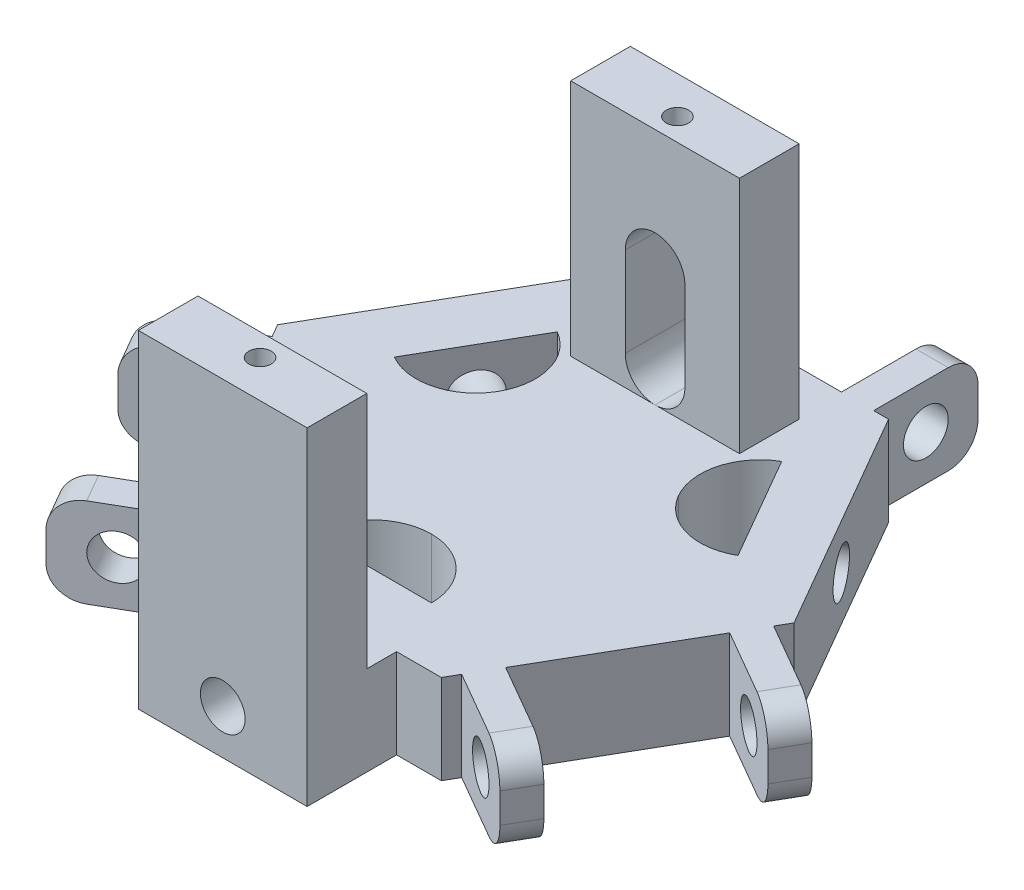
SolidWorks part; units mm, degrees
ref_plane "Front Plane" through (0, 0, 0) normal (0, 0, 1) x (1, 0, 0)
ref_plane "Top Plane" through (0, 0, 0) normal (0, 1, 0) x (1, 0, 0)
ref_plane "Right Plane" through (0, 0, 0) normal (1, 0, 0) x (0, 0, -1)
sketch "Sketch1" plane through (0, 0, 0) normal (0, 1, 0) x (1, 0, 0)
  line L1 (17.3205, 0) -> (8.6603, 15)
  line L2 (8.6603, 15) -> (-8.6603, 15)
  line L3 (-8.6603, 15) -> (-17.3205, 0)
  line L4 (-17.3205, 0) -> (-8.6603, -15)
  line L5 (-8.6603, -15) -> (8.6603, -15)
  line L6 (8.6603, -15) -> (17.3205, 0)
  circle A0 centre (0, 0) radius 15 construction
  dimension "D1" = 30
extrude "Boss-Extrude1" add sketch "Sketch1" along normal blind 6
sketch "Sketch2" plane through (12.9904, 0, 7.5) normal (0.866, 0, 0.5) x (0.5, 0, -0.866)
  line L0 (-8.6603, 6) -> (8.6603, 6) construction
  line L1 (-5.5003, 6) -> (-7.6603, 6)
  line L2 (-5.5003, 6) -> (-5.5003, 0)
  line L3 (-5.5003, 0) -> (-7.6603, 0)
  line L4 (-7.6603, 6) -> (-7.6603, 0)
  line L5 (-8.6603, 0) -> (8.6603, 0) construction
  line L6 (-8.6603, 6) -> (-8.6603, 0) construction
  dimension "D1" = 2.16
  dimension "D2" = 1
extrude "Boss-Extrude2" add sketch "Sketch2" along normal blind 7
sketch "Sketch4" plane through (12.9904, 0, 7.5) normal (0.866, 0, 0.5) x (0.5, 0, -0.866)
  line L0 (-5.5003, 6) -> (8.6603, 6) construction
  line L1 (5.5003, 6) -> (7.6603, 6)
  line L2 (5.5003, 6) -> (5.5003, 0)
  line L3 (5.5003, 0) -> (7.6603, 0)
  line L4 (7.6603, 6) -> (7.6603, 0)
  line L5 (-5.5003, 0) -> (8.6603, 0) construction
  line L6 (8.6603, 6) -> (8.6603, 0) construction
  dimension "D1" = 1
  dimension "D2" = 2.16
extrude "Boss-Extrude3" add sketch "Sketch4" along normal blind 7
sketch "Sketch5" plane through (-12.9904, 0, 7.5) normal (-0.866, 0, 0.5) x (0.5, 0, 0.866)
  line L0 (-8.6603, 6) -> (8.6603, 6) construction
  line L1 (-7.6603, 6) -> (-5.5003, 6)
  line L2 (-7.6603, 6) -> (-7.6603, 0)
  line L3 (-7.6603, 0) -> (-5.5003, 0)
  line L4 (-5.5003, 6) -> (-5.5003, 0)
  line L5 (-8.6603, 0) -> (8.6603, 0) construction
  line L6 (-8.6603, 6) -> (-8.6603, 0) construction
  dimension "D1" = 1
  dimension "D2" = 2.16
extrude "Boss-Extrude4" add sketch "Sketch5" along normal blind 7
sketch "Sketch6" plane through (-12.9904, 0, 7.5) normal (-0.866, 0, 0.5) x (0.5, 0, 0.866)
  line L0 (-5.5003, 6) -> (8.6603, 6) construction
  line L1 (5.5003, 6) -> (7.6603, 6)
  line L2 (5.5003, 6) -> (5.5003, 0)
  line L3 (5.5003, 0) -> (7.6603, 0)
  line L4 (7.6603, 6) -> (7.6603, 0)
  line L5 (-5.5003, 0) -> (8.6603, 0) construction
  line L6 (8.6603, 6) -> (8.6603, 0) construction
  dimension "D1" = 1
  dimension "D2" = 2.16
extrude "Boss-Extrude5" add sketch "Sketch6" along normal blind 7
sketch "Sketch7" plane through (0, 0, -15) normal (0, 0, -1) x (-1, 0, 0)
  line L0 (-8.6603, 6) -> (8.6603, 6) construction
  line L1 (-5.5003, 6) -> (-7.6603, 6)
  line L2 (-5.5003, 6) -> (-5.5003, 0)
  line L3 (-5.5003, 0) -> (-7.6603, 0)
  line L4 (-7.6603, 6) -> (-7.6603, 0)
  line L5 (-8.6603, 0) -> (8.6603, 0) construction
  line L6 (-8.6603, 6) -> (-8.6603, 0) construction
  dimension "D1" = 1
  dimension "D2" = 2.16
extrude "Boss-Extrude6" add sketch "Sketch7" along normal blind 7
sketch "Sketch9" plane through (0, 0, -15) normal (0, 0, -1) x (-1, 0, 0)
  line L0 (-5.5003, 6) -> (8.6603, 6) construction
  line L1 (5.5003, 6) -> (7.6603, 6)
  line L2 (5.5003, 6) -> (5.5003, 0)
  line L3 (5.5003, 0) -> (7.6603, 0)
  line L4 (7.6603, 6) -> (7.6603, 0)
  line L5 (-5.5003, 0) -> (8.6603, 0) construction
  line L6 (8.6603, 6) -> (8.6603, 0) construction
  dimension "D1" = 1
  dimension "D2" = 2.16
extrude "Boss-Extrude7" add sketch "Sketch9" along normal blind 7
sketch "Sketch11" plane through (0, 0, 15) normal (0, 0, 1) x (1, 0, 0)
  line L0 (-8.6603, 0) -> (8.6603, 0) construction
  line L1 (-5.6603, 0) -> (5.6603, 0)
  line L2 (-5.6603, 0) -> (-5.6603, 22)
  line L3 (-5.6603, 22) -> (5.6603, 22)
  line L4 (5.6603, 0) -> (5.6603, 22)
  line L5 (-8.6603, 6) -> (-8.6603, 0) construction
  line L6 (8.6603, 6) -> (8.6603, 0) construction
  point P10 (8.6603, 3)
  dimension "D1" = 22
  dimension "D2" = 3
  dimension "D3" = 3
extrude "Boss-Extrude8" add sketch "Sketch11" along normal blind 6
sketch "Sketch13" plane through (0, 22, 0) normal (0, 1, 0) x (1, 0, 0)
  line L0 (5.6603, -21) -> (5.6603, -15) construction
  line L1 (-5.6603, -15) -> (5.6603, -15)
  line L2 (-5.6603, -15) -> (-5.6603, -17)
  line L3 (-5.6603, -17) -> (5.6603, -17)
  line L4 (5.6603, -15) -> (5.6603, -17)
  dimension "D1" = 2
extrude "Cut-Extrude1" cut sketch "Sketch13" against normal blind 16
sketch "Sketch14" plane through (0, 6, 0) normal (0, 1, 0) x (1, 0, 0)
  line L0 (5.5003, 15) -> (-5.5003, 15) construction
  line L1 (-5.6603, 12) -> (5.6603, 12)
  line L2 (-5.6603, 12) -> (-5.6603, 8)
  line L3 (-5.6603, 8) -> (5.6603, 8)
  line L4 (5.6603, 12) -> (5.6603, 8)
  line L5 (5.6603, -17) -> (5.6603, -15) construction
  line L6 (-5.6603, -15) -> (-5.6603, -17) construction
  dimension "D1" = 4
  dimension "D2" = 3
  dimension "D3" = 0
  dimension "D4" = 0
extrude "Boss-Extrude9" add sketch "Sketch14" along normal blind 16
sketch "Sketch22" plane through (0, 0, -12) normal (0, 0, -1) x (-1, 0, 0)
  line L0 (-5.6603, 6) -> (5.6603, 6) construction
  line L1 (-1.9997, 16) -> (2.0003, 16)
  line L2 (-1.9997, 16) -> (-1.9997, 6)
  line L3 (-1.9997, 6) -> (2.0003, 6)
  line L4 (2.0003, 16) -> (2.0003, 6)
  line L5 (5.6603, 22) -> (5.6603, 6) construction
  dimension "D1" = 10
  dimension "D2" = 4
  dimension "D3" = 3.66
extrude "Cut-Extrude8" cut sketch "Sketch22" against normal blind 4
sketch "Sketch23" plane through (7.6603, 0, 0) normal (1, 0, 0) x (0, 0, -1)
  line L0 (22, 0) -> (15, 6) construction
  line L1 (15, 0) -> (22, 6) construction
  circle A0 centre (18.5, 3) radius 1.5
  dimension "D1" = 3
extrude "Cut-Extrude9" cut sketch "Sketch23" against normal through all
sketch "Sketch24" plane through (-3.8301, 0, 6.634) normal (-0.5, 0, 0.866) x (0.866, 0, 0.5)
  line L0 (22, 0) -> (15, 6) construction
  line L1 (15, 0) -> (22, 6) construction
  circle A0 centre (18.5, 3) radius 1.5
  dimension "D1" = 3
extrude "Cut-Extrude10" cut sketch "Sketch24" against normal through all
sketch "Sketch25" plane through (-3.8301, 0, -6.634) normal (-0.5, 0, -0.866) x (-0.866, 0, 0.5)
  line L0 (22, 0) -> (15, 6) construction
  line L1 (15, 0) -> (22, 6) construction
  circle A0 centre (18.5, 3) radius 1.5
  dimension "D1" = 3
extrude "Cut-Extrude11" cut sketch "Sketch25" against normal through all
sketch "Sketch26" plane through (0, 6, 0) normal (0, 1, 0) x (1, 0, 0)
  line L0 (-5.6603, -15) -> (-5.6603, -17) construction
  line L1 (-4.0003, -7) -> (3.9997, -7)
  line L2 (-4.0003, -7) -> (-4.0003, -11)
  line L3 (-4.0003, -11) -> (3.9997, -11)
  line L4 (3.9997, -7) -> (3.9997, -11)
  line L5 (-8.6603, -15) -> (-5.6603, -15) construction
  dimension "D1" = 8
  dimension "D2" = 1.66
  dimension "D3" = 4
  dimension "D4" = 4
extrude "Cut-Extrude12" cut sketch "Sketch26" against normal blind 6 contours L2 L1 L4 L3
fillet "Fillet1" radius 4 2 edges at (-4.0003, 3, 7) (3.9997, 3, 7)
sketch "Sketch32" plane through (0, 6, 0) normal (0, 1, 0) x (1, 0, 0)
  line L0 (10.9903, 10.9643) -> (14.9905, 4.0357)
  line L1 (10.9903, 10.9643) -> (7.5262, 8.9643)
  line L2 (14.9905, 4.0357) -> (11.5264, 2.0357)
  line L3 (7.5262, 8.9643) -> (11.5264, 2.0357)
  line L4 (17.3205, 0) -> (8.6603, 15) construction
  line L5 (7.5262, 8.9643) -> (11.5264, 2.0357)
  line L6 (7.5262, 8.9643) -> (4.0621, 6.9643)
  line L7 (11.5264, 2.0357) -> (8.0623, 0.0357)
  line L8 (4.0621, 6.9643) -> (8.0623, 0.0357)
  dimension "D1" = 4
  dimension "D2" = 4.66
  dimension "D3" = 4.66
  dimension "D4" = 4
extrude "Cut-Extrude13" cut sketch "Sketch32" against normal blind 6 contours L6 L8 L7 L3 region at (7.7942, 6, -4.5)
fillet "Fillet2" radius 4 2 edges at (8.0623, 3, -0.0357) (4.0621, 3, -6.9643)
sketch "Sketch33" plane through (0, 6, 0) normal (0, 1, 0) x (1, 0, 0)
  line L0 (-14.9905, 4.0357) -> (-10.9905, 10.9639)
  line L1 (-14.9905, 4.0357) -> (-11.5264, 2.0357)
  line L2 (-10.9905, 10.9639) -> (-7.5264, 8.9639)
  line L3 (-11.5264, 2.0357) -> (-7.5264, 8.9639)
  line L4 (-8.6603, 15) -> (-17.3205, 0) construction
  line L5 (-7.5264, 8.9639) -> (-11.5264, 2.0357)
  line L6 (-7.5264, 8.9639) -> (-4.0623, 6.9639)
  line L7 (-11.5264, 2.0357) -> (-8.0623, 0.0357)
  line L8 (-4.0623, 6.9639) -> (-8.0623, 0.0357)
  dimension "D1" = 8
  dimension "D2" = 4
  dimension "D3" = 4.66
  dimension "D4" = 4
extrude "Cut-Extrude14" cut sketch "Sketch33" against normal blind 6 contours L5 L6 L8 L7
fillet "Fillet3" radius 4 2 edges at (-8.0623, 3, -0.0357) (-4.0623, 3, -6.9639)
sketch "Sketch34" plane through (-12.9904, 0, -7.5) normal (-0.866, 0, -0.5) x (-0.5, 0, 0.866)
  line L0 (8.6603, 6) -> (-8.6603, 0) construction
  line L1 (-8.4772, 6) -> (8.6603, 0) construction
  line L2 (-9.3922, 6) -> (-7.5622, 6) construction
  circle A0 centre (0, 3) radius 1.5
  dimension "D1" = 3
extrude "Cut-Extrude15" cut sketch "Sketch34" against normal blind 4
sketch "Sketch35" plane through (12.9904, 0, -7.5) normal (0.866, 0, -0.5) x (-0.5, 0, -0.866)
  line L0 (8.6603, 6) -> (-8.6603, 0) construction
  line L1 (-8.6603, 6) -> (8.6603, 0) construction
  circle A0 centre (0, 3) radius 1.5
  dimension "D1" = 3
extrude "Cut-Extrude16" cut sketch "Sketch35" against normal blind 4
sketch "Sketch36" plane through (0, 0, 21) normal (0, 0, 1) x (1, 0, 0)
  line L0 (-5.6603, 6) -> (5.6603, 0) construction
  line L1 (-5.6603, 0) -> (5.6603, 6) construction
  circle A0 centre (0, 3) radius 1.5
  dimension "D1" = 3
extrude "Cut-Extrude17" cut sketch "Sketch36" against normal blind 10
fillet "Fillet4" radius 2 2 edges at (1.9997, 16, -10) (-2.0003, 16, -10)
fillet "Fillet5" radius 2 2 edges at (-2.0003, 6, -10) (1.9997, 6, -10)
sketch "Sketch37" plane through (0, 22, 0) normal (0, 1, 0) x (1, 0, 0)
  line L0 (-5.6603, 8) -> (5.6603, 8) construction
  circle A0 centre (0, 9.5) radius 0.75
  dimension "D1" = 1.5
  dimension "D2" = 1.5
extrude "Cut-Extrude19" cut sketch "Sketch37" against normal blind 5
sketch "Sketch39" plane through (0, 22, 0) normal (0, 1, 0) x (1, 0, 0)
  line L0 (-5.6603, -17) -> (5.6603, -17) construction
  circle A0 centre (0, -18.5) radius 0.75
  dimension "D1" = 1.5
  dimension "D2" = 1.5
extrude "Cut-Extrude20" cut sketch "Sketch39" against normal blind 5
fillet "Fillet6" radius 2 12 edges at (-22.3427, 0, 5.3013) (-22.3427, 6, 5.3013) (-15.7624, 0, 16.6987) (-15.7624, 6, 16.6987) (15.7624, 6, 16.6987) (15.7624, 0, 16.6987) (22.3427, 0, 5.3013) (22.3427, 6, 5.3013) (-6.5803, 0, -22) (-6.5803, 6, -22) (6.5803, 0, -22) (6.5803, 6, -22)
